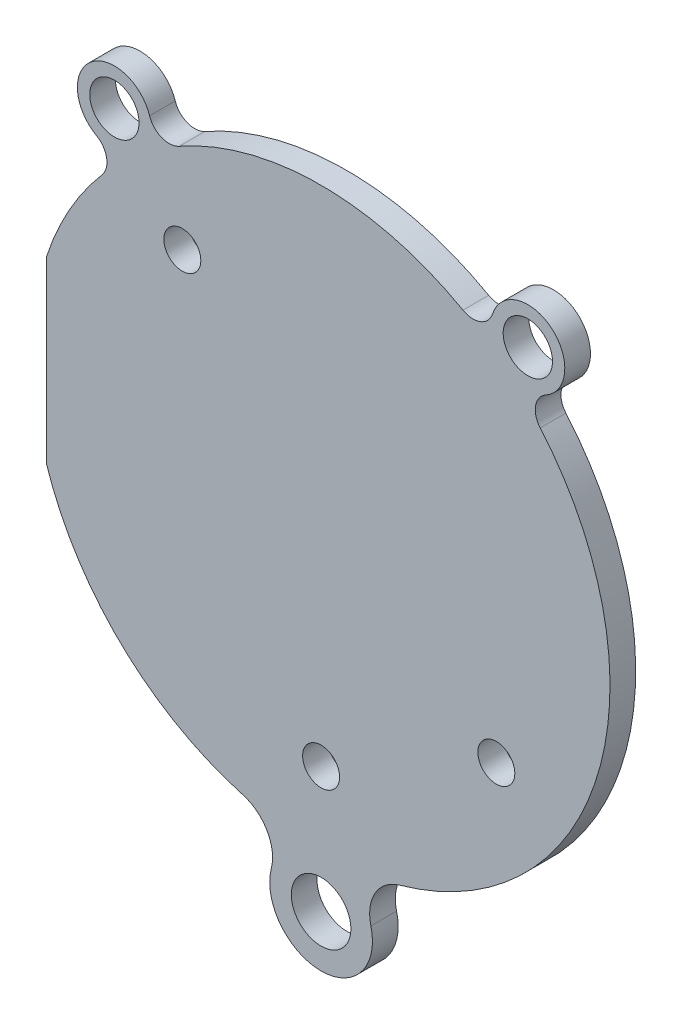
SolidWorks part; units mm, degrees
ref_plane "Front Plane" through (0, 0, 0) normal (0, 0, 1) x (1, 0, 0)
ref_plane "Top Plane" through (0, 0, 0) normal (0, 1, 0) x (1, 0, 0)
ref_plane "Right Plane" through (0, 0, 0) normal (1, 0, 0) x (0, 0, -1)
sketch "Sketch1" plane through (0, 0, 0) normal (0, 0, 1) x (1, 0, 0)
  line L7 (-16.9841, -5.5245) -> (-16.9841, 5.5245)
  arc A0 (-13.5462, 11.6395) -> (-13.8916, 13.5768) centre (-14.5094, 12.4672) ccw construction
  arc A1 (4.8506, -17.1887) -> (13.5462, 11.6395) centre (0, 0) ccw construction
  arc A2 (8.7709, 15.5579) -> (-8.7709, 15.5579) centre (0, 0) ccw construction
  arc A3 (4.8506, -17.1887) -> (3.078, -20.2562) centre (5.5404, -19.6332) ccw construction
  arc A4 (13.8916, 13.5768) -> (13.5462, 11.6395) centre (14.5094, 12.4672) ccw construction
  arc A5 (8.7709, 15.5579) -> (10.6034, 16.2749) centre (9.3946, 16.6642) ccw construction
  arc A6 (-3.078, -20.2562) -> (-4.8506, -17.1887) centre (-5.5404, -19.6332) ccw construction
  arc A7 (-13.5462, 11.6395) -> (-16.9841, 5.5245) centre (0, 0) ccw
  arc A8 (-16.9841, -5.5245) -> (-4.8506, -17.1887) centre (0, 0) ccw
  arc A9 (-3.078, -20.2562) -> (3.078, -20.2562) centre (0, -21.035) ccw construction
  arc A10 (4.8506, -17.1887) -> (13.5462, 11.6395) centre (0, 0) ccw
  arc A11 (-3.078, -20.2562) -> (-4.8506, -17.1887) centre (-5.5404, -19.6332) ccw
  arc A12 (8.7709, 15.5579) -> (-8.7709, 15.5579) centre (0, 0) ccw
  arc A13 (-3.078, -20.2562) -> (3.078, -20.2562) centre (0, -21.035) ccw
  arc A14 (4.8506, -17.1887) -> (3.078, -20.2562) centre (5.5404, -19.6332) ccw
  circle A15 centre (0, -21.035) radius 1.8415 construction
  circle A17 centre (0, -21.035) radius 1.8415
  arc A18 (-10.6034, 16.2749) -> (-13.8916, 13.5768) centre (-12.7793, 15.574) ccw construction
  circle A19 centre (-12.7793, 15.574) radius 1.524 construction
  arc A20 (-10.6034, 16.2749) -> (-8.7709, 15.5579) centre (-9.3946, 16.6642) ccw construction
  arc A22 (-13.5462, 11.6395) -> (-13.8916, 13.5768) centre (-14.5094, 12.4672) ccw
  arc A23 (-10.6034, 16.2749) -> (-13.8916, 13.5768) centre (-12.7793, 15.574) ccw
  circle A24 centre (-12.7793, 15.574) radius 1.524
  arc A25 (-10.6034, 16.2749) -> (-8.7709, 15.5579) centre (-9.3946, 16.6642) ccw
  arc A26 (13.8916, 13.5768) -> (10.6034, 16.2749) centre (12.7793, 15.574) ccw construction
  circle A27 centre (12.7793, 15.574) radius 1.524 construction
  arc A28 (13.8916, 13.5768) -> (10.6034, 16.2749) centre (12.7793, 15.574) ccw
  circle A29 centre (12.7793, 15.574) radius 1.524
  arc A30 (8.7709, 15.5579) -> (10.6034, 16.2749) centre (9.3946, 16.6642) ccw
  arc A31 (13.8916, 13.5768) -> (13.5462, 11.6395) centre (14.5094, 12.4672) ccw
extrude "Boss-Extrude1" add sketch "Sketch1" along normal blind 1.5875
sketch "Sketch2" plane through (0, 0, 1.5875) normal (0, 0, 1) x (1, 0, 0)
  circle A0 centre (-8.579, 10.1092) radius 1.143
  circle A1 centre (10.8325, -7.6454) radius 1.143
  circle A2 centre (0, -13.2588) radius 1.143
  circle A3 centre (-8.579, 10.1092) radius 1.143 construction
extrude "Cut-Extrude1" cut sketch "Sketch2" against normal through all
